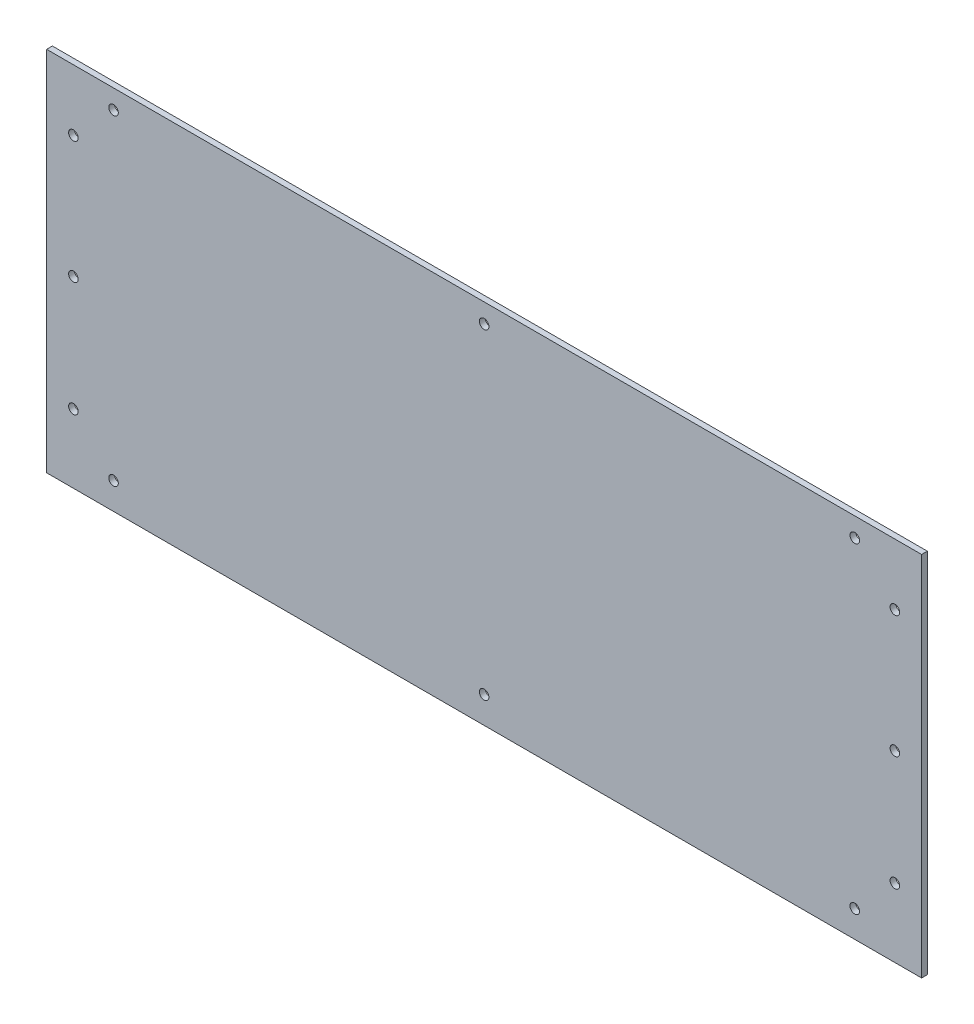
SolidWorks part; units mm, degrees
material "1345 Alloy"
ref_plane "Front Plane" through (0, 0, 0) normal (0, 0, 1) x (1, 0, 0)
ref_plane "Top Plane" through (0, 0, 0) normal (0, 1, 0) x (1, 0, 0)
ref_plane "Right Plane" through (0, 0, 0) normal (1, 0, 0) x (0, 0, -1)
sketch "Sketch1" plane through (0, 0, 0) normal (0, 0, 1) x (1, 0, 0)
  line L1 (-229, 96) -> (229, 96)
  line L2 (-229, 96) -> (-229, -96)
  line L3 (-229, -96) -> (229, -96)
  line L4 (229, 96) -> (229, -96)
  line L5 (-229, 96) -> (229, -96) construction
  line L6 (-229, -96) -> (229, 96) construction
  point P0 (0, 0)
  dimension "D1" = 458
  dimension "D2" = 192
extrude "Boss-Extrude1" add sketch "Sketch1" along normal blind 3
sketch "Sketch2" plane through (0, 0, 3) normal (0, 0, 1) x (1, 0, 0)
  line L0 (-229, 96) -> (-229, 86) construction
  line L1 (-229, 96) -> (-194, 96) construction
  line L2 (-194, 96) -> (-194, 86) construction
  line L3 (-194, 86) -> (-229, 86) construction
  line L4 (-194, -96) -> (-194, -82) construction
  line L5 (-229, -96) -> (229, -96) construction
  line L7 (194, -96.0046) -> (194, -82.0046) construction
  line L8 (194, 86) -> (194, 96) construction
  line L9 (-229, 0) -> (-215, 0) construction
  line L10 (-215, 0) -> (-215, 64) construction
  line L11 (-215, 0) -> (-215, -60) construction
  line L12 (229, 0) -> (215, 0) construction
  line L13 (0, 86) -> (-194, 86) construction
  line L14 (215, 64) -> (215, 96) construction
  line L15 (215, 0) -> (215, 64) construction
  line L16 (215, 0) -> (215, -60) construction
  line L17 (0, 86) -> (194, 86) construction
  line L18 (229, 96) -> (-229, 96) construction
  line L20 (-194, -82.0046) -> (0, -82.0046) construction
  line L22 (-215, 64) -> (-215, 96) construction
  circle A0 centre (-194, 86) radius 2.5
  circle A1 centre (-194, -82.0046) radius 2.5
  circle A2 centre (194, -82.0046) radius 2.5
  circle A3 centre (194, 86) radius 2.5
  circle A4 centre (-215, 0) radius 2.5
  circle A5 centre (-215, -60) radius 2.5
  circle A6 centre (-215, 64) radius 2.5
  circle A7 centre (215, 0) radius 2.5
  circle A8 centre (215, -60) radius 2.5
  circle A9 centre (215, 64) radius 2.5
  circle A10 centre (0, 86) radius 2.5
  circle A11 centre (0, -82.0046) radius 2.5
  dimension "D3" = 5
  dimension "D6" = 5
  dimension "D7" = 5
  dimension "D8" = 5
  dimension "D13" = 5
  dimension "D14" = 5
  dimension "D15" = 5
  dimension "D19" = 5
  dimension "D20" = 5
  dimension "D1" = 10
  dimension "D2" = 35
  dimension "D4" = 14
  dimension "D9" = 14
  dimension "D10" = 14
  dimension "D11" = 64
  dimension "D12" = 60
  dimension "D16" = 14
  dimension "D17" = 64
  dimension "D18" = 60
  dimension "D22" = 194
  dimension "D23" = 194
  dimension "D24" = 32
  dimension "D25" = 32
extrude "Cut-Extrude1" cut sketch "Sketch2" against normal through all
